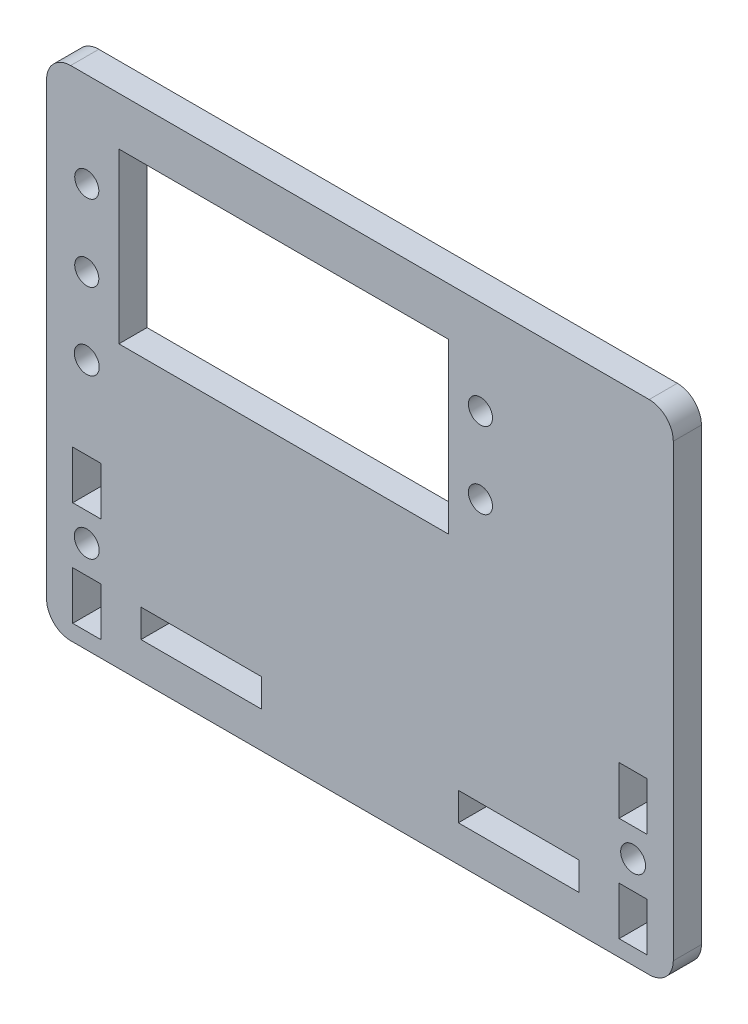
SolidWorks part; units mm, degrees
material "Balsa"
ref_plane "Front Plane" through (0, 0, 0) normal (0, 0, 1) x (1, 0, 0)
ref_plane "Top Plane" through (0, 0, 0) normal (0, 1, 0) x (1, 0, 0)
ref_plane "Right Plane" through (0, 0, 0) normal (1, 0, 0) x (0, 0, -1)
sketch "Sketch1" plane through (0, 0, 0) normal (0, 0, 1) x (1, 0, 0)
  line L1 (-36, -31) -> (36, -31)
  line L2 (-39, -28) -> (-39, 28)
  line L3 (-36, 31) -> (36, 31)
  line L4 (39, -28) -> (39, 28)
  line L5 (0, 31) -> (0, -31) construction
  line L6 (-39, 0) -> (39, 0) construction
  line L7 (-30, 4) -> (11, 4)
  line L8 (-30, 4) -> (-30, 25)
  line L9 (-30, 25) -> (11, 25)
  line L10 (11, 4) -> (11, 25)
  arc A0 (36, 31) -> (39, 28) centre (36, 28) cw
  arc A1 (36, -31) -> (39, -28) centre (36, -28) ccw
  arc A2 (-36, -31) -> (-39, -28) centre (-36, -28) cw
  arc A3 (-39, 28) -> (-36, 31) centre (-36, 28) cw
  point P0 (0, 0)
  point P8 (39, -31)
  point P12 (-39, -31)
  dimension "D2" = 3
  dimension "D3" = 62
  dimension "D1" = 28
  dimension "D4" = 41
  dimension "D5" = 21
  dimension "D6" = 9
  dimension "D7" = 6
extrude "Boss-Extrude1" add sketch "Sketch1" along normal blind 3.5
sketch "Sketch2" plane through (0, 0, 3.5) normal (0, 0, 1) x (1, 0, 0)
  line L0 (-39, -19.5) -> (39, -19.5) construction
  line L1 (-36, -31) -> (36, -31) construction
  line L2 (39, -28) -> (39, 28) construction
  line L3 (-39, 28) -> (-39, -28) construction
  line L4 (34, -29.922) -> (34, 0) construction
  line L5 (32.25, -16) -> (35.75, -16)
  line L6 (32.25, -16) -> (32.25, -10)
  line L7 (32.25, -10) -> (35.75, -10)
  line L8 (35.75, -16) -> (35.75, -10)
  line L9 (35.75, -23) -> (32.25, -23)
  line L10 (35.75, -23) -> (35.75, -29)
  line L11 (35.75, -29) -> (32.25, -29)
  line L12 (32.25, -23) -> (32.25, -29)
  line L13 (0, 10.4666) -> (0, -9.03) construction
  line L14 (-35.75, -23) -> (-32.25, -23)
  line L15 (-32.25, -23) -> (-32.25, -29)
  line L16 (-35.75, -29) -> (-32.25, -29)
  line L17 (-35.75, -23) -> (-35.75, -29)
  line L18 (-32.25, -16) -> (-35.75, -16)
  line L19 (-32.25, -16) -> (-32.25, -10)
  line L20 (-32.25, -10) -> (-35.75, -10)
  line L21 (-35.75, -16) -> (-35.75, -10)
  circle A1 centre (34, -19.5) radius 1.55
  circle A2 centre (-34, -19.5) radius 1.55
  dimension "D2" = 0
  dimension "D9" = 3.1
  dimension "D1" = 11.5
  dimension "D3" = 6
  dimension "D4" = 3.5
  dimension "D5" = 6
  dimension "D6" = 19
  dimension "D8" = 5
extrude "Cut-Extrude1" cut sketch "Sketch2" against normal through all
sketch "Sketch3" plane through (0, 0, 3.5) normal (0, 0, 1) x (1, 0, 0)
  line L0 (-32.25, -23) -> (32.25, -23) construction
  line L1 (0, 0) -> (0, -31) construction
  line L2 (-27.25, -23) -> (-12.25, -23)
  line L3 (-27.25, -23) -> (-27.25, -26.5)
  line L4 (-27.25, -26.5) -> (-12.25, -26.5)
  line L5 (-12.25, -23) -> (-12.25, -26.5)
  line L6 (-36, -31) -> (36, -31) construction
  line L8 (27.25, -23) -> (27.25, -26.5)
  line L9 (27.25, -23) -> (12.25, -23)
  line L10 (12.25, -23) -> (12.25, -26.5)
  line L11 (27.25, -26.5) -> (12.25, -26.5)
  dimension "D1" = 24.5
  dimension "D2" = 15
  dimension "D3" = 3.5
extrude "Cut-Extrude2" cut sketch "Sketch3" against normal through all
sketch "Sketch4" plane through (0, 0, 3.5) normal (0, 0, 1) x (1, 0, 0)
  line L0 (-32.7283, 14.5) -> (20.2148, 14.5) construction
  line L1 (11, 25) -> (-30, 25) construction
  line L2 (-9.5, -1.2649) -> (-9.5, 28.2785) construction
  line L3 (-30, 4) -> (11, 4) construction
  line L4 (-30, 25) -> (-30, 4) construction
  line L5 (11, 4) -> (11, 25) construction
  line L7 (-34, 9.75) -> (15, 9.75) construction
  line L8 (-34, 9.75) -> (-34, 19.25) construction
  line L9 (-34, 19.25) -> (15, 19.25) construction
  line L10 (15, 9.75) -> (15, 19.25) construction
  line L11 (-9.5, 19.25) -> (-9.5, 9.75) construction
  line L12 (-34, 14.5) -> (15, 14.5) construction
  circle A0 centre (15, 19.25) radius 1.5
  circle A1 centre (15, 9.75) radius 1.5
  circle A2 centre (-34, 9.75) radius 1.5
  circle A3 centre (-34, 19.25) radius 1.5
  point P12 (-9.5, 14.5)
  dimension "D3" = 3
  dimension "D1" = 9.5
  dimension "D2" = 49
extrude "Cut-Extrude3" cut sketch "Sketch4" against normal through all both and the other way through all
sketch "Sketch5" plane through (0, 0, 3.5) normal (0, 0, 1) x (1, 0, 0)
  line L0 (-34, 31) -> (-34, -31) construction
  line L3 (36, 31) -> (-36, 31) construction
  line L6 (-36, -31) -> (36, -31) construction
  circle A2 centre (-34, 0.25) radius 1.55
  circle A7 centre (-34, 9.75) radius 1.5 construction
  dimension "D1" = 9.5
extrude "Cut-Extrude4" cut sketch "Sketch5" against normal up to next contours A2
